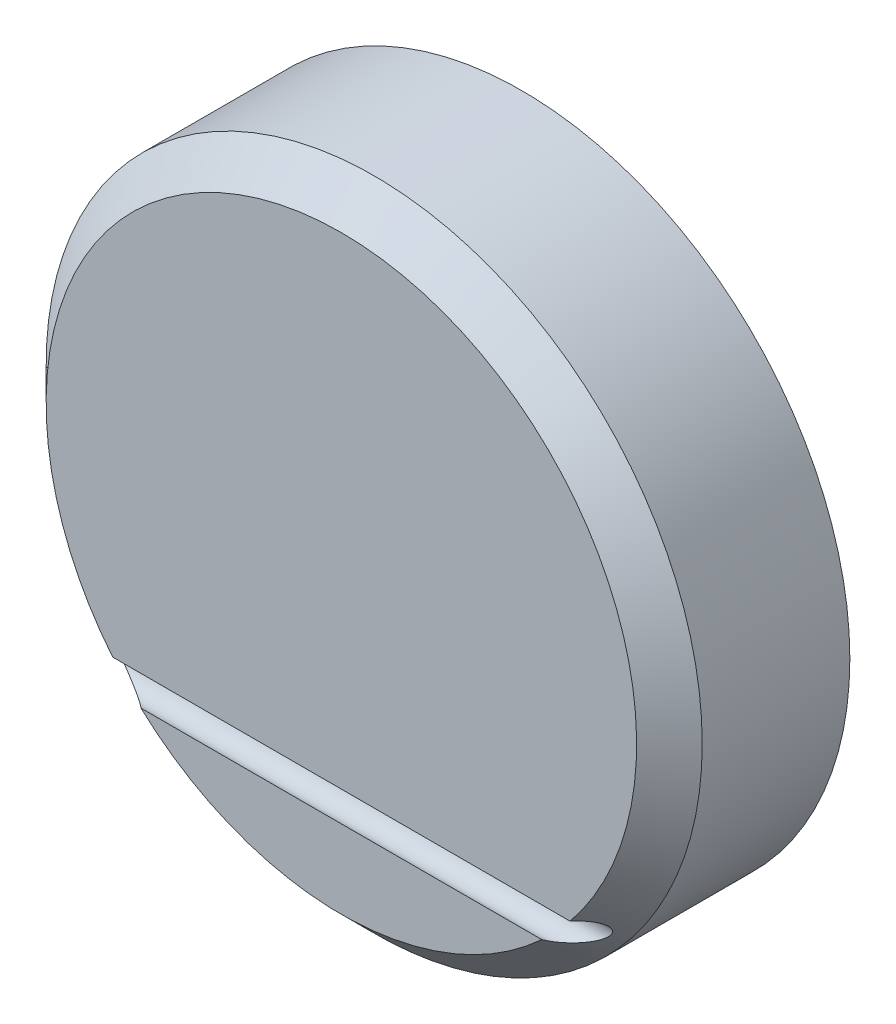
SolidWorks part; units mm, degrees
ref_plane "Front Plane" through (0, 0, 0) normal (0, 0, 1) x (1, 0, 0)
ref_plane "Top Plane" through (0, 0, 0) normal (0, 1, 0) x (1, 0, 0)
ref_plane "Right Plane" through (0, 0, 0) normal (1, 0, 0) x (0, 0, -1)
sketch "Sketch1" plane through (0, 0, 0) normal (0, 0, 1) x (1, 0, 0)
  circle A0 centre (0, 0) radius 8.25
  circle A1 centre (0, 0) radius 10
  dimension "D1" = 16.5
  dimension "D2" = 20
extrude "Boss-Extrude1" add sketch "Sketch1" against normal blind 4.5 contours A1 A0 region at (-9.7172, 0, 0)
extrude "Boss-Extrude2" add sketch "Sketch1<3>" against normal blind 1 contours A0 region at (0, 0, 0)
sketch "Sketch1<3>" plane through (0, 0, 0) normal (0, 0, 1) x (1, 0, 0) same geometry as "Sketch1"
sketch "Sketch2" plane through (0, 0, -4.5) normal (0, 0, -1) x (-1, 0, 0)
  circle A0 centre (0, 0) radius 9.2
  circle A1 centre (0, 0) radius 10
  circle A2 centre (0, 0) radius 10
  dimension "D1" = 0
  dimension "D2" = 0.8
extrude "Boss-Extrude3" add sketch "Sketch2" along normal blind 1
chamfer "Chamfer1" distance 1 angle 45 1 edges at (10, 0, 0)
chamfer "Chamfer2" distance 0.5 angle 45 1 edges at (8.25, 0, -1)
sketch "Sketch4" plane through (0, 0, 0) normal (1, 0, 0) x (0, 0, -1)
  circle A0 centre (0.2, -6.15) radius 0.5
  dimension "D1" = 1
  dimension "D2" = 6.15
  dimension "D3" = 0.2
extrude "Cut-Extrude3" cut sketch "Sketch4" against normal through all both and the other way through all
